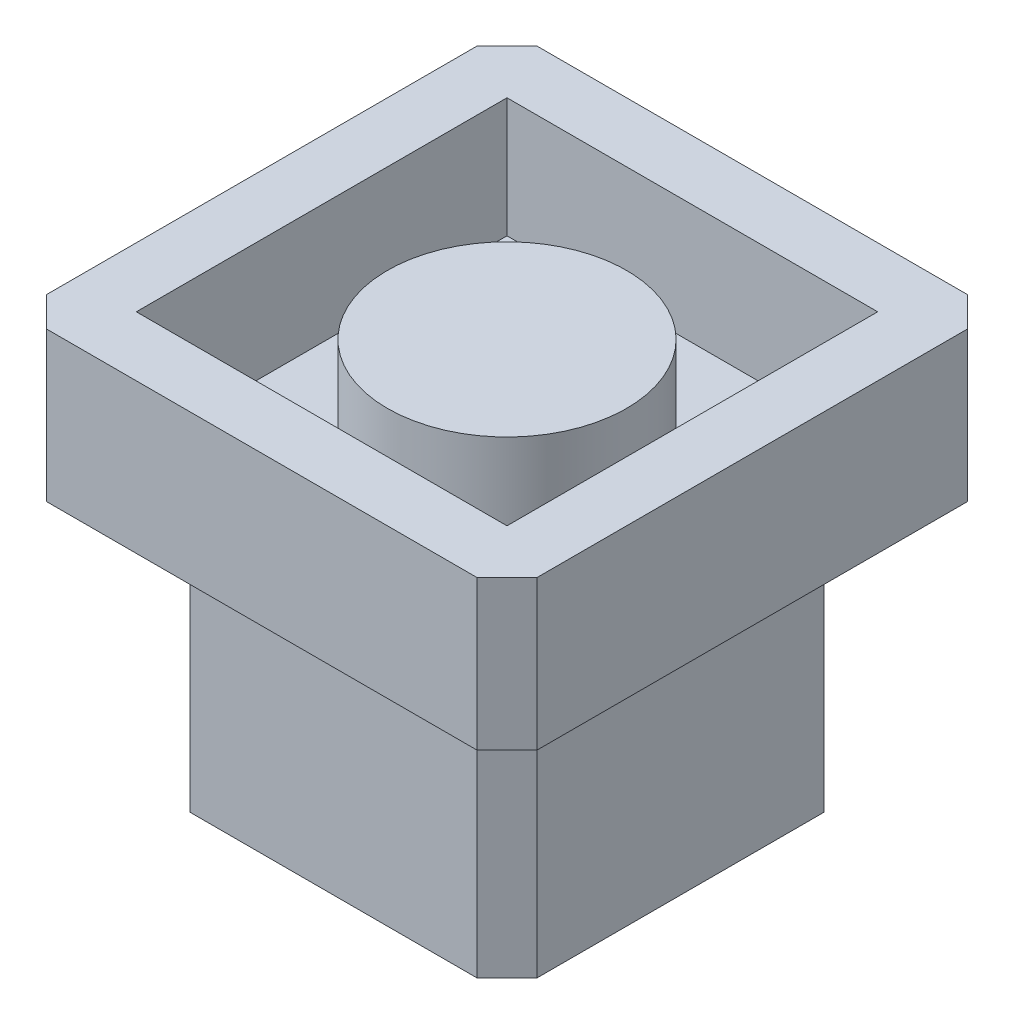
SolidWorks part; units mm, degrees
ref_plane "Front Plane" through (0, 0, 0) normal (0, 0, 1) x (1, 0, 0)
ref_plane "Top Plane" through (0, 0, 0) normal (0, 1, 0) x (1, 0, 0)
ref_plane "Right Plane" through (0, 0, 0) normal (1, 0, 0) x (0, 0, -1)
sketch "Sketch1" plane through (0, 0, 0) normal (0, 1, 0) x (1, 0, 0)
  line L0 (-4.1, 4.1) -> (-4.1, -4.1)
  line L1 (-3.1, 3.1) -> (3.1, 3.1)
  line L2 (-3.1, 3.1) -> (-3.1, -3.1)
  line L3 (-3.1, -3.1) -> (3.1, -3.1)
  line L4 (3.1, 3.1) -> (3.1, -3.1)
  line L5 (-3.1, 3.1) -> (3.1, -3.1) construction
  line L6 (-3.1, -3.1) -> (3.1, 3.1) construction
  line L7 (-4.1, -4.1) -> (4.1, -4.1)
  line L8 (4.1, 4.1) -> (4.1, -4.1)
  line L9 (-4.1, 4.1) -> (4.1, 4.1)
  circle A1 centre (0, 0) radius 2
  dimension "D1" = 4
  dimension "D2" = 6.2
  dimension "D3" = 1
extrude "Boss-Extrude1" add sketch "Sketch1" along normal blind 1.6 contours A1 region at (0, 0, 0)
extrude "Boss-Extrude2" add sketch "Sketch1<3>" along normal blind 2 separate body contours L9 L0 L7 L8 L1 L4 L3 L2 region at (0, 0, -3.984)
sketch "Sketch1<3>" plane through (0, 0, 0) normal (0, 1, 0) x (1, 0, 0) same geometry as "Sketch1"
extrude "Boss-Extrude3" add sketch "Sketch1<4>" against normal blind 0.5 contours L9 L0 L7 L8 L1 L4 L3 L2 | L4 L1 L2 L3 A1 | A1 region at (0, 0, -3.984) region at (0, 0, -3.0123) region at (0, 0, 0)
sketch "Sketch1<4>" plane through (0, 0, 0) normal (0, 1, 0) x (1, 0, 0) same geometry as "Sketch1"
sketch "Sketch3" plane through (0, -0.5, 0) normal (0, -1, 0) x (1, 0, 0)
  line L1 (-2.9, 2.9) -> (2.9, 2.9)
  line L2 (-2.9, 2.9) -> (-2.9, -2.9)
  line L3 (-2.9, -2.9) -> (2.9, -2.9)
  line L4 (2.9, 2.9) -> (2.9, -2.9)
  line L5 (-2.9, 2.9) -> (2.9, -2.9) construction
  line L6 (-2.9, -2.9) -> (2.9, 2.9) construction
  point P0 (0, 0)
  dimension "D1" = 5.8
  dimension "D2" = 5.8
extrude "Boss-Extrude4" add sketch "Sketch3" along normal blind 4.5
chamfer "Chamfer1" distance 0.5 angle 45 8 edges at (-4.1, 0.75, -4.1) (4.1, 0.75, -4.1) (-4.1, 0.75, 4.1) (4.1, 0.75, 4.1) (-2.9, -2.75, 2.9) (2.9, -2.75, 2.9) (-2.9, -2.75, -2.9) (2.9, -2.75, -2.9)
sketch "Sketch4" plane through (0, -5, 0) normal (0, -1, 0) x (1, 0, 0)
  text T0 "R"
extrude "Cut-Extrude1" cut sketch "Sketch4" against normal blind 0.2
